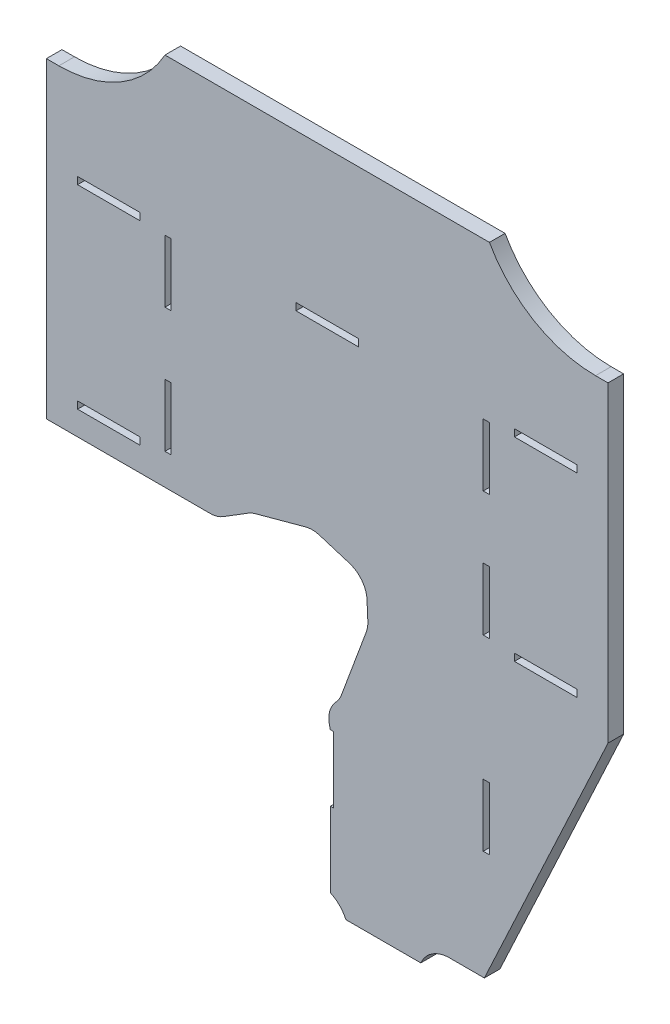
SolidWorks part; units mm, degrees
material "PBT General Purpose"
ref_plane "Front Plane" through (0, 0, 0) normal (0, 0, 1) x (1, 0, 0)
ref_plane "Top Plane" through (0, 0, 0) normal (0, 1, 0) x (1, 0, 0)
ref_plane "Right Plane" through (0, 0, 0) normal (1, 0, 0) x (0, 0, -1)
sketch "frame_outline" plane through (0, 0, 0) normal (0, 0, 1) x (1, 0, 0)
  line L0 (0, 0) -> (0, 0.3) construction
  line L1 (0, 0) -> (0.3, 0) construction
  line L2 (0, 0.3) -> (0.05, 0.3) construction
  line L3 (0.3, 0) -> (0.3, 0.05) construction
  line L4 (0.05, 0.3) -> (0.05, 1.5)
  line L5 (0.05, 1.5) -> (0.1, 1.5)
  line L6 (0.05, 0.3) -> (0.3, 0.3)
  line L7 (0.3, 0.3) -> (0.3, 0.05)
  line L8 (0.3, 0.05) -> (1.5, 0.05)
  line L9 (1.5, 0.05) -> (1.5, 0.35)
  line L10 (1.5, 0.35) -> (2.5182, 0.35)
  line L11 (2.5182, 0.35) -> (4.5, 4.6)
  line L12 (4.5, 4.6) -> (4.5, 10.6)
  line L13 (4.5, 10.6) -> (-4.5, 10.6)
  line L14 (-4.5, 10.6) -> (-4.5, 4.6)
  line L15 (-4.5, 4.6) -> (-1.7637, 4.6)
  line L16 (-1.7637, 4.6) -> (-1.2133, 4.9416)
  line L18 (0.1, 2.5625) -> (0.1, 1.5)
  line L19 (0, 10.6) -> (0, 0) construction
  line L20 (-2.5, 8.1) -> (2.5, 8.1) construction
  line L21 (-3, 5.0425) -> (3, 5.0425) construction
  line L22 (-0.5, 8.215) -> (0.5, 8.215)
  line L23 (-2.5, 8.1) -> (-2.6, 8.1)
  line L24 (-2.5, 8.1) -> (-2.5, 7.1)
  line L25 (-2.5, 7.1) -> (-2.6, 7.1)
  line L26 (-2.6, 8.1) -> (-2.6, 7.1)
  line L27 (-2.6, 6.1) -> (-2.5, 6.1)
  line L28 (-2.6, 6.1) -> (-2.6, 5.1)
  line L29 (-2.6, 5.1) -> (-2.5, 5.1)
  line L30 (-2.5, 6.1) -> (-2.5, 5.1)
  line L31 (2.5, 8.1) -> (2.6, 8.1)
  line L32 (2.5, 8.1) -> (2.5, 7.1)
  line L33 (2.5, 7.1) -> (2.6, 7.1)
  line L34 (2.6, 8.1) -> (2.6, 7.1)
  line L35 (2.5, 6.1) -> (2.6, 6.1)
  line L36 (2.5, 6.1) -> (2.5, 5.1)
  line L37 (2.5, 5.1) -> (2.6, 5.1)
  line L38 (2.6, 6.1) -> (2.6, 5.1)
  line L39 (2.5, 3.1) -> (2.6, 3.1)
  line L40 (2.5, 3.1) -> (2.5, 2.1)
  line L41 (2.5, 2.1) -> (2.6, 2.1)
  line L42 (2.6, 3.1) -> (2.6, 2.1)
  line L43 (-0.5, 8.215) -> (-0.5, 8.1)
  line L44 (-0.5, 8.1) -> (0.5, 8.1)
  line L45 (0.5, 8.215) -> (0.5, 8.1)
  line L46 (-4, 8.215) -> (-3, 8.215)
  line L47 (-4, 8.215) -> (-4, 8.1)
  line L48 (-4, 8.1) -> (-3, 8.1)
  line L49 (-3, 8.215) -> (-3, 8.1)
  line L50 (3, 8.215) -> (4, 8.215)
  line L51 (3, 8.215) -> (3, 8.1)
  line L52 (3, 8.1) -> (4, 8.1)
  line L53 (4, 8.215) -> (4, 8.1)
  line L54 (-4, 5.1) -> (-3, 5.1)
  line L55 (-4, 5.1) -> (-4, 4.985)
  line L56 (-4, 4.985) -> (-3, 4.985)
  line L57 (-3, 5.1) -> (-3, 4.985)
  line L58 (3, 5.1) -> (4, 5.1)
  line L59 (3, 5.1) -> (3, 4.985)
  line L60 (3, 4.985) -> (4, 4.985)
  line L61 (4, 5.1) -> (4, 4.985)
  line L62 (-3, 8.1575) -> (3, 8.1575) construction
  line L63 (0.1, 2.5625) -> (0.05, 2.5625)
  line L64 (0.05, 2.5625) -> (-0.0089, 2.8119)
  line L65 (-0.0089, 2.8119) -> (0.2035, 3.0663)
  line L66 (0.2035, 3.0663) -> (0.655, 4.2832)
  line L67 (0.655, 4.2832) -> (0.6251, 4.9416)
  line L68 (0.6251, 4.9416) -> (-0.2329, 5.2084)
  line L69 (-0.2329, 5.2084) -> (-1.2133, 4.9416)
  line L71 (-0.5, 4.985) -> (0.5, 4.985) construction
  line L72 (-0.5, 4.985) -> (-0.5, 5.1) construction
  line L73 (-0.5, 5.1) -> (0.5, 5.1) construction
  line L74 (0.5, 4.985) -> (0.5, 5.1) construction
  point P40 (0, 8.1)
  point P53 (0, 8.215)
  point P64 (0, 5.0425)
  point P65 (0, 8.1575)
  point P87 (2.55, 2.1)
  dimension "D2" = 0.3
  dimension "D3" = 0.05
  dimension "D4" = 0.05
  dimension "D5" = 1.2
  dimension "D6" = 1.2
  dimension "D7" = 0.05
  dimension "D8" = 0.3
  dimension "D10" = 9
  dimension "D13" = 6
  dimension "D14" = 10.6
  dimension "D15" = 6
  dimension "D16" = 5
  dimension "D17" = 0.1
  dimension "D18" = 0.1
  dimension "D19" = 1
  dimension "D20" = 1
  dimension "D21" = 1
  dimension "D22" = 2.5
  dimension "D23" = 1
  dimension "D24" = 0.115
  dimension "D25" = 1
  dimension "D26" = 1
  dimension "D27" = 0.115
  dimension "D28" = 3
  dimension "D29" = 3
  dimension "D30" = 2
  dimension "D9" = 155
  dimension "D11" = 0.0318
extrude "Boss-Extrude1" add sketch "frame_outline" along normal mid plane 0.25
fillet "Fillet1" radius 0.5 2 edges at (1.5, 0.35, 0) (0.3, 0.3, 0)
fillet "Fillet2" radius 0.4 7 edges at (-1.7637, 4.6, 0) (-1.2133, 4.9416, 0) (-0.2329, 5.2084, 0) (0.6251, 4.9416, 0) (0.655, 4.2832, 0) (0.2035, 3.0663, 0) (-0.0089, 2.8119, 0)
sketch "Sketch1" plane through (0, 0, 0.125) normal (0, 0, 1) x (1, 0, 0)
  line L0 (-4.5, 9.6) -> (-4.5, 10.6)
  line L1 (-4.5, 10.6) -> (-4.5, 4.6) construction
  line L2 (-4.5, 10.6) -> (-2.6, 10.6)
  line L3 (4.5, 10.6) -> (-4.5, 10.6) construction
  line L6 (-4.3, 9.6) -> (-4.5, 9.6)
  line L7 (4.5, 10.6) -> (4.5, 9.6)
  line L8 (4.5, 4.6) -> (4.5, 10.6) construction
  line L9 (4.5, 9.6) -> (4.3, 9.6)
  line L12 (2.6, 10.6) -> (4.5, 10.6)
  arc A0 (-4.3, 9.6) -> (-2.6, 10.6) centre (-4.3, 11.545) ccw
  arc A1 (4.3, 9.6) -> (2.6, 10.6) centre (4.3, 11.545) cw
  dimension "D1" = 1
  dimension "D2" = 1
  dimension "D3" = 1.9
  dimension "D4" = 1.9
  dimension "D5" = 0.2
  dimension "D6" = 0.2
extrude "Cut-Extrude1" cut sketch "Sketch1" against normal through all
equation "\"t\"= 0.25'thickness of the sheets"
equation "\"t_cf\"= 0.115'thickness of single carbon fiber layer"
equation "\"t_kapton\"= 0.025'thickness of single Kapton flex layer"
equation "\"t_fr4\"= 0.1'thickness of FR4 with copper layer"
equation "\"joint_flex\"= 0.1'Width of flextures gap"
equation "\"joint_flex_eff\"= 0.02'Width of flecture after castelation"
equation "\"joint_fold\"= 0.2'Width of folding joints for 90deg fold"
equation "\"gap_tolerance\"= 0.002'Width to have interfecence fit between carbon fiber inserts"
equation "\"assemble_angle\"= 90'Angle of assembly parts"
equation "\"D3@frame_outline\" = \"joint_flex\" / 2"
equation "\"D4@frame_outline\" = \"joint_flex\" / 2"
equation "\"D17@frame_outline\" = \"t_fr4\""
equation "\"D18@frame_outline\" = \"t_fr4\""
equation "\"D24@frame_outline\" = \"t_cf\""
equation "\"D27@frame_outline\" = \"t_cf\""
equation "\"D1@Boss-Extrude1\"=\"t\""
equation "\"link_lift\"= 0.5'Actuation linkage amplification for the lift motion"
equation "\"link_swing\"= 0.45'Actuation linkage amplification for the swing motion"
